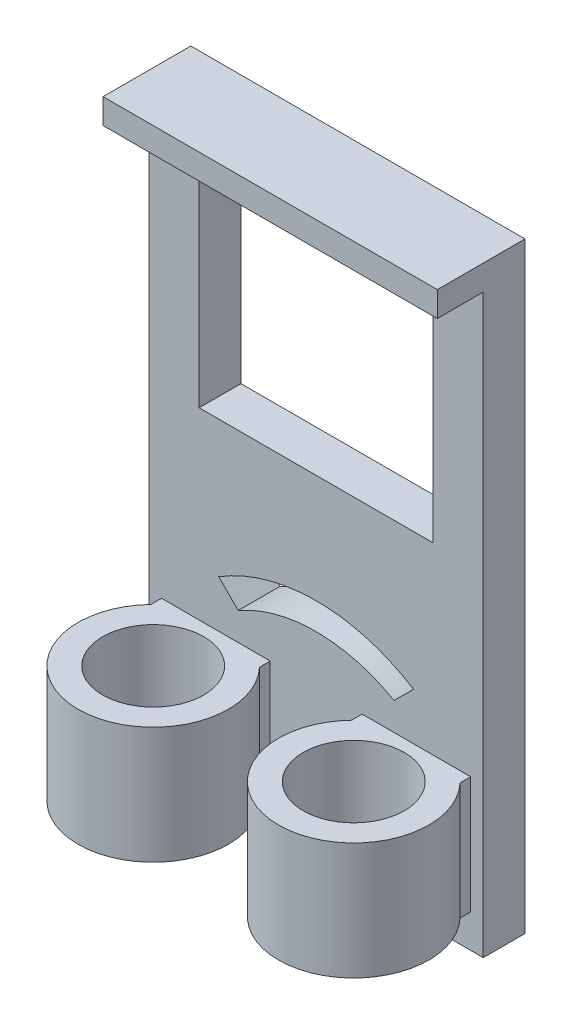
SolidWorks part; units mm, degrees
ref_plane "Front Plane" through (0, 0, 0) normal (0, 0, 1) x (1, 0, 0)
ref_plane "Top Plane" through (0, 0, 0) normal (0, 1, 0) x (1, 0, 0)
ref_plane "Right Plane" through (0, 0, 0) normal (1, 0, 0) x (0, 0, -1)
sketch "Sketch1" plane through (0, 0, 0) normal (0, 0, 1) x (1, 0, 0)
  line L1 (20, -20) -> (-20, -20)
  line L2 (20, -20) -> (20, 20)
  line L3 (20, 20) -> (-20, 20)
  line L4 (-20, -20) -> (-20, 20)
  line L5 (20, -20) -> (-20, 20) construction
  line L6 (20, 20) -> (-20, -20) construction
  point P0 (0, 0)
  dimension "D1" = 40
extrude "Boss-Extrude2" add sketch "Sketch1" along normal blind 2
sketch "Sketch2" plane through (0, 0, 2) normal (0, 0, 1) x (1, 0, 0)
  line L0 (-12, 0) -> (-12, 10) construction
  line L1 (0, 0) -> (-12, 0) construction
  line L2 (-15, 12) -> (-9, 12)
  line L3 (-15, 12) -> (-15, 8)
  line L4 (-15, 8) -> (-9, 8)
  line L5 (-9, 12) -> (-9, 8)
  line L6 (-15, 12) -> (-9, 8) construction
  line L7 (-15, 8) -> (-9, 12) construction
  point P1 (-12, 10)
  dimension "D1" = 10
  dimension "D2" = 4
  dimension "D3" = 6
  dimension "D4" = 12
extrude "Boss-Extrude5" add sketch "Sketch2" along normal blind 3
sketch "Sketch4" plane through (0, 12, 0) normal (0, 1, 0) x (1, 0, 0)
  line L1 (-9, -5) -> (-15, -5) construction
  circle A0 centre (-12, -6.6) radius 1.6
  circle A1 centre (-12, -6.6) radius 3.5
  point P9 (-12, -5)
  dimension "D1" = 3.2
  dimension "D2" = 7
  dimension "D3" = 1.6
extrude "Boss-Extrude6" add sketch "Sketch4" against normal blind 4
ref_plane "Plane2" through (0, 3, 0) normal (0, -1, 0) x (-1, 0, 0)
mirror "Mirror2" about plane through (0, 0, 0) normal (1, 0, 0) of "Boss-Extrude5", "Boss-Extrude6" second plane through (0, 3, 0) second plane normal (0, -1, 0)
sketch "Sketch6" plane through (0, 0, 2) normal (0, 0, 1) x (1, 0, 0)
  line L0 (-20, 20) -> (-15, 20)
  line L1 (20, 20) -> (-20, 20) construction
  line L2 (-15, 20) -> (-15, -20)
  line L3 (-20, -20) -> (20, -20) construction
  line L4 (-15, -20) -> (-20, -20)
  line L5 (-20, -20) -> (-20, 20)
  line L6 (20, 20) -> (15, 20)
  line L7 (15, 20) -> (15, -20)
  line L8 (15, -20) -> (20, -20)
  line L9 (20, -20) -> (20, 20)
  dimension "D1" = 5
  dimension "D2" = 5
  dimension "D4" = 5
extrude "Cut-Extrude1" [suppressed] cut sketch "Sketch6" against normal blind 3 contours L5 L0 L2 L4 | L9 L6 L7 L8
sketch "Sketch7" plane through (0, 0, 2) normal (0, 0, 1) x (1, 0, 0)
  line L0 (0, 0) -> (0, -15)
  line L1 (0, 0) -> (0, 7) construction
  line L2 (-8, 0) -> (8, 0) construction
  line L3 (9.3246, 1.3246) -> (11.6575, 3.6575)
  line L4 (-9.3246, 1.3246) -> (-11.6575, 3.6575)
  line L5 (-8, 0) -> (-9.3246, 1.3246) construction
  line L6 (8, 0) -> (9.3246, 1.3246) construction
  arc A0 (11.6575, 3.6575) -> (-11.6575, 3.6575) centre (0, -15) ccw
  arc A1 (9.3246, 1.3246) -> (-9.3246, 1.3246) centre (0, -15) ccw
  arc A2 (-9.3246, 1.3246) -> (9.3246, 1.3246) centre (0, -15) ccw construction
  arc A3 (-11.6575, 3.6575) -> (11.6575, 3.6575) centre (0, -15) ccw construction
  point P9 (0, 0)
  dimension "D1" = 15
  dimension "D2" = 7
  dimension "D3" = 3.2
  dimension "D4" = 8
  dimension "D5" = 45
  dimension "D6" = 45
extrude "Cut-Extrude2" cut sketch "Sketch7" against normal blind 2 contours A1 L3 A0 L4 region at (0, 4.477, 2)
sketch "Sketch8" plane through (0, 0, 0) normal (0, 0, -1) x (-1, 0, 0)
  line L0 (0, 0) -> (0, -10) construction
  circle A0 centre (0, -10) radius 1.6
  dimension "D1" = 10
  dimension "D2" = 3.2
extrude "Cut-Extrude3" cut sketch "Sketch8" against normal blind 2
sketch "Sketch18" plane through (0, 20, 0) normal (0, 1, 0) x (1, 0, 0)
  line L0 (20, -2) -> (-20, -2) construction
  line L1 (-20, 0) -> (-14, 0)
  line L2 (-20, 0) -> (-20, -2)
  line L3 (-20, -2) -> (-14, -2)
  line L4 (-14, 0) -> (-14, -2)
  line L6 (20, -2) -> (14, -2)
  line L7 (20, -2) -> (20, 0)
  line L8 (20, 0) -> (14, 0)
  line L9 (14, -2) -> (14, 0)
  line L10 (20, 0) -> (-20, 0) construction
  line M5 (20, 0) -> (-20, 0)
  line M6 (-20, 0) -> (-20, -2)
  line M7 (-20, -2) -> (20, -2)
  line M8 (20, -2) -> (20, 0)
  dimension "D2" = 6
  dimension "D1" = 6
extrude "Boss-Extrude10" add sketch "Sketch18" along normal blind 32 contours M7 M8 M5 | M6 M7 region at (-17, 20, 1) region at (17, 20, 1)
sketch "Sketch19" plane through (0, 52, 0) normal (0, 1, 0) x (1, 0, 0)
  line L13 (-20, 0) -> (20, 0)
  line L14 (-20, 0) -> (-20, -3.5)
  line L15 (-20, -3.5) -> (20, -3.5)
  line L16 (20, 0) -> (20, -3.5)
  line M10 (-14, 0) -> (-20, 0)
  line M11 (-20, 0) -> (-20, -2)
  line M12 (-20, -2) -> (-14, -2)
  dimension "D2" = 40
  dimension "D1" = 3.5
extrude "Boss-Extrude11" add sketch "Sketch19" against normal blind 3 contours M12 | M12 M10 M11 region at (0, 52, 1.75)
sketch "Sketch20" plane through (0, -6, 0) normal (0, -1, 0) x (1, 0, 0)
  line L3 (-9, 2) -> (-9, 4.7972)
  line L4 (-15, 4.7972) -> (-15, 2)
  line L5 (-15, 2) -> (-9, 2)
  line L6 (-9, 2) -> (-9, 4.7972)
  line L7 (-15, 4.7972) -> (-15, 2)
  line L8 (-15, 2) -> (-9, 2)
  line L9 (9, 4.7972) -> (9, 2)
  line L10 (9, 2) -> (15, 2)
  line L11 (15, 2) -> (15, 4.7972)
  line L12 (9, 4.7972) -> (9, 2)
  line L13 (9, 2) -> (15, 2)
  line L14 (15, 2) -> (15, 4.7972)
  circle A0 centre (-12, 6.6) radius 1.6 construction
  arc A1 (-9, 4.7972) -> (-15, 4.7972) centre (-12, 6.6) ccw
  arc A2 (-9, 4.7972) -> (-15, 4.7972) centre (-12, 6.6) ccw
  arc A3 (15, 4.7972) -> (9, 4.7972) centre (12, 6.6) ccw
  arc A4 (15, 4.7972) -> (9, 4.7972) centre (12, 6.6) ccw
  circle A5 centre (-12, 6.6) radius 1.6
  circle A6 centre (12, 6.6) radius 1.6 construction
  circle A7 centre (12, 6.6) radius 1.6
  dimension "D1" = 0
  dimension "D2" = 0
extrude "Boss-Extrude12" add sketch "Sketch20" along normal blind 10
sketch "Sketch21" plane through (0, 12, 0) normal (0, 1, 0) x (1, 0, 0)
  line L0 (9, -2) -> (9, -4.7972) construction
  line L1 (15, -4.7972) -> (15, -2) construction
  line L2 (15, -2) -> (9, -2) construction
  line L3 (-9, -4.7972) -> (-9, -2) construction
  line L4 (-9, -2) -> (-15, -2) construction
  line L5 (-15, -2) -> (-15, -4.7972) construction
  line L6 (9, -2) -> (9, -4.7972)
  line L7 (15, -4.7972) -> (15, -2)
  line L8 (15, -2) -> (9, -2)
  line L9 (-9, -4.7972) -> (-9, -2)
  line L10 (-9, -2) -> (-15, -2)
  line L11 (-15, -2) -> (-15, -4.7972)
  arc A0 (9, -4.7972) -> (15, -4.7972) centre (12, -6.6) ccw construction
  arc A1 (-15, -4.7972) -> (-9, -4.7972) centre (-12, -6.6) ccw construction
  circle A2 centre (-12, -6.6) radius 1.6 construction
  circle A3 centre (12, -6.6) radius 1.6 construction
  arc A4 (9, -4.7972) -> (15, -4.7972) centre (12, -6.6) ccw
  arc A5 (-15, -4.7972) -> (-9, -4.7972) centre (-12, -6.6) ccw
  circle A6 centre (-12, -6.6) radius 1.6
  circle A7 centre (12, -6.6) radius 1.6
sketch "Sketch22" plane through (0, -2, 0) normal (0, 1, 0) x (1, 0, 0)
  line L3 (9, -2) -> (9, -4.7972)
  line L4 (15, -4.7972) -> (15, -2)
  line L5 (15, -2) -> (9, -2)
  line L6 (9, -2) -> (9, -4.7972)
  line L7 (15, -4.7972) -> (15, -2)
  line L8 (15, -2) -> (9, -2)
  line L9 (-9, -4.7972) -> (-9, -2)
  line L10 (-9, -2) -> (-15, -2)
  line L11 (-15, -2) -> (-15, -4.7972)
  line L12 (-9, -4.7972) -> (-9, -2)
  line L13 (-9, -2) -> (-15, -2)
  line L14 (-15, -2) -> (-15, -4.7972)
  circle A0 centre (12, -6.6) radius 1.6 construction
  arc A1 (9, -4.7972) -> (15, -4.7972) centre (12, -6.6) ccw
  arc A2 (9, -4.7972) -> (15, -4.7972) centre (12, -6.6) ccw
  circle A3 centre (12, -6.6) radius 1.6
  circle A4 centre (-12, -6.6) radius 1.6 construction
  arc A5 (-15, -4.7972) -> (-9, -4.7972) centre (-12, -6.6) ccw
  arc A6 (-15, -4.7972) -> (-9, -4.7972) centre (-12, -6.6) ccw
  circle A7 centre (-12, -6.6) radius 1.6
  dimension "D1" = 0
  dimension "D2" = 0
extrude "Cut-Extrude4" cut sketch "Sketch22" against normal blind 7
sketch "Sketch23" plane through (0, -16, 0) normal (0, -1, 0) x (1, 0, 0)
  line L0 (-15, 2) -> (-9, 2) construction
  line L1 (-20, 2) -> (20, 2) construction
  line L2 (-15, 2) -> (-9, 2)
  line L3 (-17, 2) -> (-7, 2)
  line L4 (-7, 2) -> (-7, 3.9098)
  line L5 (-17, 2) -> (-17, 3.9098)
  line L6 (0, -5.555) -> (0, 5.555) construction
  line L7 (17, 2) -> (17, 3.9098)
  line L8 (7, 2) -> (7, 3.9098)
  line L9 (17, 2) -> (7, 2)
  line L10 (15, 2) -> (9, 2)
  circle A0 centre (-12, 9.5) radius 6.05
  arc A1 (-7, 3.9098) -> (-17, 3.9098) centre (-12, 9.5) ccw
  arc A2 (7, 3.9098) -> (17, 3.9098) centre (12, 9.5) cw
  circle A3 centre (12, 9.5) radius 6.05
  point P10 (-12, 2)
  point P11 (-12, 2)
  line M8 (-15, 2) -> (-9, 2)
  line M9 (-9, 2) -> (-9, 4.7972)
  line M11 (-15, 4.7972) -> (-15, 2)
  dimension "D1" = 12.1
  dimension "D2" = 15
  dimension "D3" = 10
extrude "Boss-Extrude14" add sketch "Sketch23" against normal blind 14 contours L4 A1 L5 L3 A0 M11 M9 | A0 M11 M8 M9 | A2 L8 L9 L7 A3 region at (-12, -16, 2.8701) region at (-16, -16, 2.2121) region at (16, -16, 2.2121)
extrude "Cut-Extrude5" cut sketch "Sketch21" against normal blind 10
sketch "Sketch24" plane through (0, -9, 0) normal (0, 1, 0) x (1, 0, 0)
  line L2 (9, -4.2462) -> (9, -4.7972)
  line L3 (15, -4.7972) -> (15, -4.2462)
  line L4 (9, -4.2462) -> (9, -4.7972)
  line L5 (15, -4.7972) -> (15, -4.2462)
  line L6 (-9, -4.7972) -> (-9, -4.2462)
  line L7 (-15, -4.2462) -> (-15, -4.7972)
  line L8 (-9, -4.7972) -> (-9, -4.2462)
  line L9 (-15, -4.2462) -> (-15, -4.7972)
  arc A2 (15, -4.2462) -> (9, -4.2462) centre (12, -9.5) ccw
  arc A3 (9, -4.7972) -> (15, -4.7972) centre (12, -6.6) ccw
  arc A4 (15, -4.2462) -> (9, -4.2462) centre (12, -9.5) ccw
  arc A5 (9, -4.7972) -> (15, -4.7972) centre (12, -6.6) ccw
  arc A6 (-9, -4.2462) -> (-15, -4.2462) centre (-12, -9.5) ccw
  arc A7 (-15, -4.7972) -> (-9, -4.7972) centre (-12, -6.6) ccw
  arc A8 (-9, -4.2462) -> (-15, -4.2462) centre (-12, -9.5) ccw
  arc A9 (-15, -4.7972) -> (-9, -4.7972) centre (-12, -6.6) ccw
  dimension "D1" = 0
  dimension "D2" = 0
extrude "Cut-Extrude7" cut sketch "Sketch24" against normal blind 22
sketch "Sketch25" plane through (0, -16, 0) normal (0, -1, 0) x (1, 0, 0)
  line L3 (-17, 2) -> (-7, 2)
  line L4 (-7, 2) -> (-7, 3.9098)
  line L5 (-17, 3.9098) -> (-17, 2)
  line L6 (-17, 2) -> (-7, 2)
  line L7 (-7, 2) -> (-7, 3.9098)
  line L8 (-17, 3.9098) -> (-17, 2)
  line L12 (7, 3.9098) -> (7, 2)
  line L13 (7, 2) -> (17, 2)
  line L14 (17, 2) -> (17, 3.9098)
  line L15 (7, 3.9098) -> (7, 2)
  line L16 (7, 2) -> (17, 2)
  line L17 (17, 2) -> (17, 3.9098)
  arc A1 (-7, 3.9098) -> (-17, 3.9098) centre (-12, 9.5) ccw
  arc A2 (-7, 3.9098) -> (-17, 3.9098) centre (-12, 9.5) ccw
  arc A4 (17, 3.9098) -> (7, 3.9098) centre (12, 9.5) ccw
  arc A5 (17, 3.9098) -> (7, 3.9098) centre (12, 9.5) ccw
  dimension "D1" = 0
  dimension "D2" = 0
sketch "Sketch26" plane through (0, -2, 0) normal (0, 1, 0) x (1, 0, 0)
  line L0 (-16, -2) -> (-8, -2) construction
  line L1 (-16, -2) -> (-16, -6.5)
  line L2 (-8, -2) -> (-8, -6.5)
  line L3 (-7, -2) -> (-17, -2)
  line L4 (-17, -2) -> (-17, -3.9098)
  line L5 (-7, -3.9098) -> (-7, -2)
  line L6 (-7, -2) -> (-17, -2)
  line L8 (-7, -3.9098) -> (-7, -2)
  line L9 (-16, -2) -> (-8, -2)
  line L10 (0, -9.35) -> (0, 9.35) construction
  line L11 (16, -2) -> (16, -6.5)
  line L12 (16, -2) -> (8, -2)
  line L13 (8, -2) -> (8, -6.5)
  circle A0 centre (-12, -9.5) radius 3.15
  arc A1 (-17, -3.9098) -> (-7, -3.9098) centre (-12, -9.5) ccw
  arc A3 (-16, -6.5) -> (-8, -6.5) centre (-12, -9.5) ccw
  circle A4 centre (12, -9.5) radius 3.15
  arc A5 (16, -6.5) -> (8, -6.5) centre (12, -9.5) cw
  point P10 (-12, -2)
  circle M14 centre (-12, -9.5) radius 6.05
  dimension "D2" = 6.3
  dimension "D3" = 10
  dimension "D4" = 4.5
  dimension "D1" = 0
extrude "Boss-Extrude17" [suppressed] add sketch "Sketch26" along normal blind 15 contours A5 L11 L12 L13 A4 | L1 A3 L2 A0 M14 | A3 L2 L9 L1 | A0
sketch "Sketch30" [suppressed] plane through (-20, 0, 0) normal (-1, 0, 0) x (0, 0, 1)
  line L1 (2, -6) -> (14.5, -6)
  line L2 (2, -6) -> (2, 4)
  line L3 (2, 4) -> (14.5, 4)
  line L4 (14.5, -6) -> (14.5, 4)
  line L5 (14.5, -6) -> (14.5, 9) construction
  dimension "D1" = 10
  dimension "D2" = 12.5
extrude "Cut-Extrude8" [suppressed] cut sketch "Sketch30" against normal blind 43
extrude "Cut-Extrude9" cut sketch "Sketch25" against normal blind 2
sketch "Sketch32" plane through (0, -14, 0) normal (0, -1, 0) x (1, 0, 0)
  line L3 (7, 3.9098) -> (7, 2)
  line L4 (7, 2) -> (17, 2)
  line L5 (17, 2) -> (17, 3.9098)
  line L6 (7, 3.9098) -> (7, 2)
  line L7 (7, 2) -> (17, 2)
  line L8 (17, 2) -> (17, 3.9098)
  line L9 (-17, 3.9098) -> (-17, 2)
  line L10 (-17, 2) -> (-7, 2)
  line L11 (-7, 2) -> (-7, 3.9098)
  line L12 (-17, 3.9098) -> (-17, 2)
  line L13 (-17, 2) -> (-7, 2)
  line L14 (-7, 2) -> (-7, 3.9098)
  circle A0 centre (-12, 9.5) radius 3.5
  arc A1 (17, 3.9098) -> (7, 3.9098) centre (12, 9.5) ccw
  arc A2 (17, 3.9098) -> (7, 3.9098) centre (12, 9.5) ccw
  arc A3 (-7, 3.9098) -> (-17, 3.9098) centre (-12, 9.5) ccw
  arc A4 (-7, 3.9098) -> (-17, 3.9098) centre (-12, 9.5) ccw
  circle A5 centre (12, 9.5) radius 3.5
  dimension "D3" = 7
  dimension "D4" = 7
  dimension "D1" = 0
  dimension "D2" = 0
extrude "Boss-Extrude19" add sketch "Sketch32" along normal blind 2
sketch "Sketch33" plane through (0, 0, 3.5) normal (0, 0, 1) x (1, 0, 0)
  line L4 (20, 52) -> (-20, 52)
  line L5 (-20, 52) -> (-20, 49)
  line L6 (-20, 49) -> (20, 49)
  line L7 (20, 49) -> (20, 52)
  line L8 (20, 52) -> (-20, 52)
  line L9 (-20, 52) -> (-20, 49)
  line L10 (-20, 49) -> (20, 49)
  line L11 (20, 49) -> (20, 52)
  dimension "D1" = 0
extrude "Boss-Extrude20" add sketch "Sketch33" along normal blind 4
sketch "Sketch34" plane through (0, 0, 0) normal (0, 0, -1) x (-1, 0, 0)
  line L0 (-9.3246, 1.3246) -> (-11.6575, 3.6575) construction
  line L1 (-14, 49) -> (-14, 20) construction
  line L2 (14, 49) -> (-14, 49) construction
  line L3 (14, 49) -> (14, 20) construction
  line L4 (20, -20) -> (20, 52)
  line L5 (20, 52) -> (-20, 52)
  line L6 (-20, 52) -> (-20, -20)
  line L7 (-20, -20) -> (20, -20)
  line L8 (20, -20) -> (20, 52)
  line L9 (20, 52) -> (-20, 52)
  line L10 (-20, 52) -> (-20, -20)
  line L11 (-20, -20) -> (20, -20)
  line L12 (-14, 20) -> (14, 20) construction
  line L13 (-9.3246, 1.3246) -> (-11.6575, 3.6575)
  line L14 (-14, 49) -> (-14, 20)
  line L15 (14, 49) -> (-14, 49)
  line L16 (14, 49) -> (14, 20)
  line L17 (-14, 20) -> (14, 20)
  circle A0 centre (0, -10) radius 1.6 construction
  arc A1 (9.3246, 1.3246) -> (-9.3246, 1.3246) centre (0, -15) ccw construction
  arc A2 (11.6575, 3.6575) -> (-11.6575, 3.6575) centre (0, -15) ccw construction
  circle A3 centre (0, -10) radius 1.6
  arc A4 (9.3246, 1.3246) -> (-9.3246, 1.3246) centre (0, -15) ccw
  arc A5 (11.6575, 3.6575) -> (-11.6575, 3.6575) centre (0, -15) ccw
  line M5 (-14, 20) -> (-14, 49)
  line M6 (-14, 49) -> (14, 49)
  line M7 (14, 49) -> (14, 20)
  line M8 (14, 20) -> (-14, 20)
  line M9 (20, -20) -> (20, 52)
  line M10 (20, 52) -> (-20, 52)
  line M11 (-20, 52) -> (-20, -20)
  line M12 (-20, -20) -> (20, -20)
  circle M13 centre (0, -10) radius 1.6
  arc M14 (9.3246, 1.3246) -> (-9.3246, 1.3246) centre (0, -15) ccw
  line M15 (-9.3246, 1.3246) -> (-11.6575, 3.6575)
  arc M16 (-11.6575, 3.6575) -> (11.6575, 3.6575) centre (0, -15) cw
  line M17 (11.6575, 3.6575) -> (9.3246, 1.3246)
  dimension "D1" = 0
extrude "Boss-Extrude21" add sketch "Sketch34" along normal blind 3 contours M12 M9 M10 M11 M13 M17 M14 M15 M16 M8 M5 M6 M7 region at (0, 8.9627, 0)
sketch "Sketch35" plane through (0, -16, 0) normal (0, -1, 0) x (1, 0, 0)
  line L0 (-18.5, 3.2751) -> (-18.5, 0.5)
  line L1 (-18.5, 0.5) -> (-5.5, 0.5)
  line L2 (-5.5, 0.5) -> (-5.5, 3.2751)
  line L3 (-17, 3.9098) -> (-17, 2)
  line L4 (-17, 2) -> (-7, 2)
  line L5 (-7, 2) -> (-7, 3.9098)
  line L6 (-17, 3.9098) -> (-17, 2)
  line L7 (-17, 2) -> (-7, 2)
  line L8 (-7, 2) -> (-7, 3.9098)
  line L9 (7, 3.9098) -> (7, 2)
  line L10 (7, 2) -> (17, 2)
  line L11 (17, 2) -> (17, 3.9098)
  line L12 (7, 3.9098) -> (7, 2)
  line L13 (7, 2) -> (17, 2)
  line L14 (17, 2) -> (17, 3.9098)
  line L15 (5.5, 3.2751) -> (5.5, 0.5)
  line L16 (5.5, 0.5) -> (18.5, 0.5)
  line L17 (18.5, 0.5) -> (18.5, 3.2751)
  arc A0 (-5.5, 3.2751) -> (-18.5, 3.2751) centre (-12, 9.5) ccw
  arc A1 (-7, 3.9098) -> (-17, 3.9098) centre (-12, 9.5) ccw
  arc A2 (-7, 3.9098) -> (-17, 3.9098) centre (-12, 9.5) ccw
  arc A3 (17, 3.9098) -> (7, 3.9098) centre (12, 9.5) ccw
  arc A4 (17, 3.9098) -> (7, 3.9098) centre (12, 9.5) ccw
  arc A5 (18.5, 3.2751) -> (5.5, 3.2751) centre (12, 9.5) ccw
  dimension "D1" = 0
  dimension "D2" = 0
  dimension "D3" = 1.5
extrude "Boss-Extrude22" add sketch "Sketch35" against normal up to surface (14 mm away) up to face at (-12, -2, 6.2275)
sketch "Sketch38" plane through (0, -16, 0) normal (0, -1, 0) x (1, 0, 0)
  line L0 (-19.4833, 14.5) -> (-4.5167, 14.5) construction
  line L1 (4.5167, 14.5) -> (19.4833, 14.5) construction
  line L2 (-12, 9.5) -> (-19.4833, 14.5)
  line L3 (-18.5, 3.2751) -> (-18.5, 2)
  line L4 (-18.5, 2) -> (-5.5, 2)
  line L5 (-5.5, 2) -> (-5.5, 3.2751)
  line L6 (-18.5, 3.2751) -> (-18.5, 2) construction
  line L7 (-18.5, 2) -> (-5.5, 2) construction
  line L8 (-5.5, 2) -> (-5.5, 3.2751) construction
  line L9 (5.5, 3.2751) -> (5.5, 2)
  line L10 (5.5, 2) -> (18.5, 2)
  line L11 (18.5, 2) -> (18.5, 3.2751)
  line L12 (5.5, 3.2751) -> (5.5, 2) construction
  line L13 (5.5, 2) -> (18.5, 2) construction
  line L14 (18.5, 2) -> (18.5, 3.2751) construction
  line L15 (-12, 9.5) -> (-4.5167, 14.5)
  line L16 (12, 9.5) -> (4.5167, 14.5)
  line L17 (12, 9.5) -> (19.4833, 14.5)
  arc A1 (-5.5, 3.2751) -> (-18.5, 3.2751) centre (-12, 9.5) ccw
  arc A2 (-4.5167, 14.5) -> (-19.4833, 14.5) centre (-12, 9.5) ccw
  arc A3 (18.5, 3.2751) -> (5.5, 3.2751) centre (12, 9.5) ccw
  arc A4 (19.4833, 14.5) -> (4.5167, 14.5) centre (12, 9.5) ccw
  arc A7 (-19.4833, 14.5) -> (-18.5, 3.2751) centre (-12, 9.5) ccw construction
  arc A8 (-5.5, 3.2751) -> (-4.5167, 14.5) centre (-12, 9.5) ccw construction
  arc A9 (4.5167, 14.5) -> (5.5, 3.2751) centre (12, 9.5) ccw construction
  arc A10 (18.5, 3.2751) -> (19.4833, 14.5) centre (12, 9.5) ccw construction
  point P13 (-12, 14.5)
  point P16 (12, 14.5)
  dimension "D3" = 5
  dimension "D1" = 0
  dimension "D2" = 0
